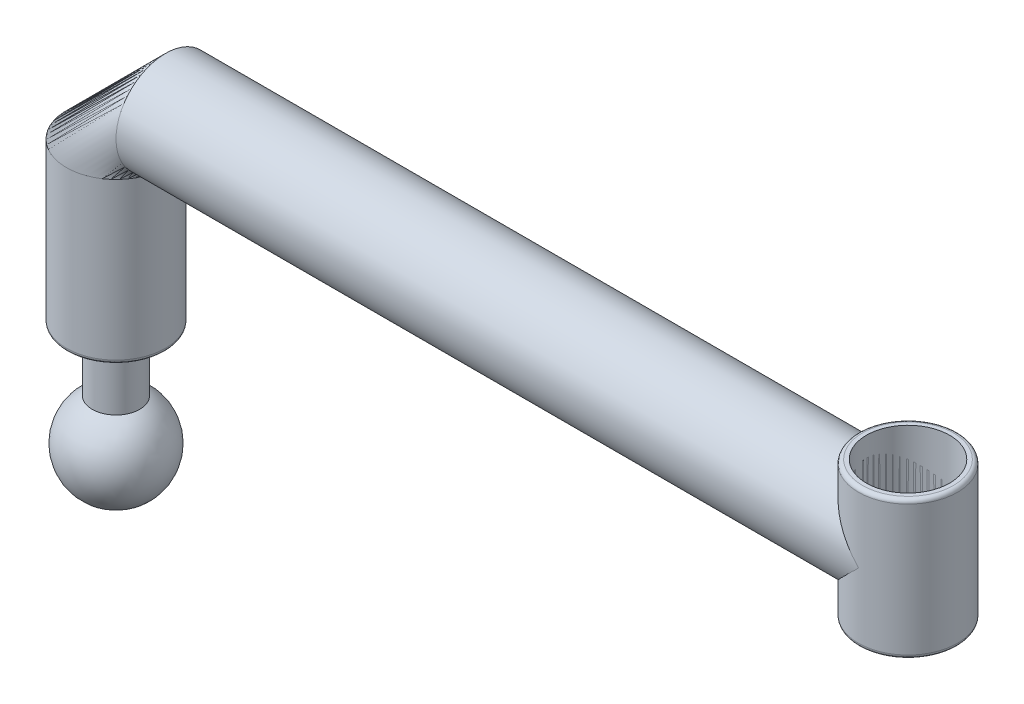
SolidWorks part; units mm, degrees
ref_plane "前基準面" through (0, 0, 0) normal (0, 0, 1) x (1, 0, 0)
ref_plane "上基準面" through (0, 0, 0) normal (0, 1, 0) x (1, 0, 0)
ref_plane "右基準面" through (0, 0, 0) normal (1, 0, 0) x (0, 0, -1)
sketch "草圖1" plane through (0, 0, 0) normal (0, 0, 1) x (1, 0, 0)
  line L0 (0, 12) -> (0, -12)
  arc A0 (0, -12) -> (0, 12) centre (0, 0) ccw
  dimension "D1" = 12
revolve "旋轉1" add sketch "草圖1" angle 360 about L0
sketch "草圖2" plane through (0, 0, 0) normal (0, 1, 0) x (1, 0, 0)
  circle A0 centre (0, 0) radius 6
  dimension "D1" = 12
extrude "填料-伸長1" add sketch "草圖2" along normal blind 26
sketch "草圖3" plane through (0, 26, 0) normal (0, 1, 0) x (1, 0, 0)
  circle A0 centre (0, 0) radius 12.5
  dimension "D1" = 25
sketch "草圖4" plane through (0, 0, 0) normal (0, 0, 1) x (1, 0, 0)
  line L0 (0, 26) -> (0, 66.5)
  line L1 (12.5, 79) -> (200, 79)
  line L2 (200, 79) -> (200, 61.5)
  arc A0 (0, 66.5) -> (12.5, 79) centre (12.5, 66.5) cw
  point P0 (0, 26)
  dimension "D1" = 12.5
  dimension "D2" = 200
  dimension "D4" = 17.5
  dimension "D5" = 53
sweep "掃出1" add profiles "草圖3" path "草圖4"
sketch "草圖5" plane through (0, 0, 0) normal (0, 0, 1) x (1, 0, 0)
  line L1 (200, 61.5) -> (200, 79)
  line L2 (200, 66.5) -> (200, 91.5) construction
  line L3 (200, 79) -> (200, 96.5)
  dimension "D1" = 17.5
  dimension "D2" = 17.5
ref_plane "平面1" through (0, 96.5, 0) normal (0, 1, 0) x (1, 0, 0)
sketch "草圖6" plane through (0, 96.5, 0) normal (0, 1, 0) x (1, 0, 0)
  line L0 (200, -12.5) -> (200, 12.5) construction
  circle A0 centre (200, 0) radius 12.5
  dimension "D1" = 25
sweep "掃出2" add profiles "草圖6" path "草圖5"
shell "薄殼1" thickness 2 removed face at (200, 96.5, 12.5)
sketch "草圖7" plane through (0, 63.5, 0) normal (0, 1, 0) x (1, 0, 0)
  circle A1 centre (200, 0) radius 10.5
  circle A2 centre (200, 0) radius 10.5
  dimension "D1" = 0
extrude "除料-伸長1" cut sketch "草圖7" along normal through all
ref_plane "平面2" through (0, 0, 0) normal (0, 0, 1) x (1, 0, 0)
ref_plane "平面3" through (0, 0, 0) normal (1, 0, 0) x (0, 0, -1)
fillet "圓角1" radius 1 1 edges at (0, 26, 12.5)
fillet "圓角2" radius 1 2 edges at (200, 96.5, 12.5) (200, 61.5, 12.5)
sketch "草圖8" plane through (0, 0, 0) normal (0, 0, 1) x (1, 0, 0)
  point P0 (0, 0)
